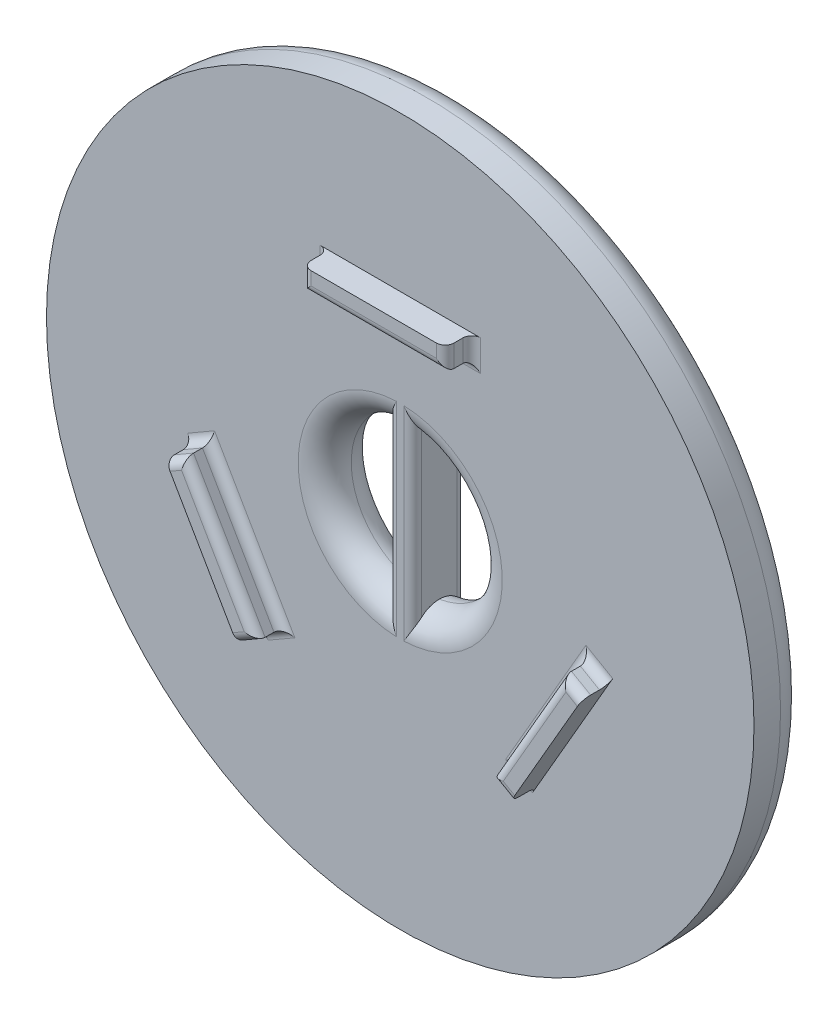
SolidWorks part; units mm, degrees
ref_plane "Front Plane" through (0, 0, 0) normal (0, 0, 1) x (1, 0, 0)
ref_plane "Top Plane" through (0, 0, 0) normal (0, 1, 0) x (1, 0, 0)
ref_plane "Right Plane" through (0, 0, 0) normal (1, 0, 0) x (0, 0, -1)
sketch "Sketch1" plane through (0, 0, 0) normal (0, 0, 1) x (1, 0, 0)
  line L4 (1.4118, -15.9376) -> (1.4118, 15.9376)
  line L8 (-1.4118, 15.9376) -> (-1.4118, -15.9376)
  circle A0 centre (0, 0) radius 40
  arc A1 (-1.4118, 15.9376) -> (-1.4118, -15.9376) centre (0, 0) ccw
  arc A2 (1.4118, -15.9376) -> (1.4118, 15.9376) centre (0, 0) ccw
  dimension "D1" = 80
  dimension "D2" = 24
sketch "Sketch3" plane through (0, 0, 0) normal (0, 0, 1) x (1, 0, 0)
  line L1 (-18.4752, -20) -> (-11.547, -20)
  line L3 (13.2791, -17) -> (17.3205, -10)
  line L4 (-13.2791, -17) -> (-17.3205, -10)
  line L6 (17.3205, -10) -> (21.362, -3)
  line L7 (21.362, -3) -> (13.2791, -17)
  line L8 (0, 20) -> (8.0829, 20)
  line L9 (8.0829, 20) -> (-8.0829, 20)
  line L10 (-17.3205, -10) -> (-21.362, -3)
  line L11 (-21.362, -3) -> (-13.2791, -17)
  line L12 (21.362, -3) -> (26.5581, -6)
  line L13 (0, 20) -> (-8.0829, 20)
  line L15 (0, 26) -> (-8.0829, 26)
  line L16 (-8.0829, 20) -> (-8.0829, 26)
  line L17 (0, 20) -> (8.0829, 20)
  line L19 (0, 26) -> (8.0829, 26)
  line L20 (8.0829, 20) -> (8.0829, 26)
  line L21 (26.5581, -6) -> (18.4752, -20)
  line L22 (18.4752, -20) -> (13.2791, -17)
  line L23 (-21.362, -3) -> (-26.5581, -6)
  line L24 (-26.5581, -6) -> (-18.4752, -20)
  line L25 (-18.4752, -20) -> (-13.2791, -17)
  line L26 (0, 20) -> (0, 0)
  circle A0 centre (0, 0) radius 40 construction
  dimension "D2" = 20
  dimension "D4" = 6
  dimension "D5" = 6
  dimension "D6" = 6
extrude "Boss-Extrude2" add sketch "Sketch3" along normal blind 3 contours L8 L20 L19 L15 L16 L9 | L22 L21 L12 L6 L3 | L24 L25 L4 L10 L23 region at (19.9186, -11.5, 0) region at (-19.9186, -11.5, 0) region at (0, 23, 0)
extrude "Boss-Extrude3" add sketch "Sketch1" against normal blind 6
fillet "Fillet1" radius 3 1 edges at (40, 0, -6)
fillet "Fillet2" radius 3 2 edges at (16, 0, -6) (-16, 0, -6)
fillet "Fillet3" radius 1 2 edges at (-1.4118, 0, -6) (1.4118, 0, -6)
fillet "Fillet4" radius 1 2 edges at (1.4118, 0, 0) (-1.4118, 0, 0)
fillet "Fillet5" radius 3 2 edges at (16, 0, 0) (-16, 0, 0)
fillet "Fillet6" radius 1 9 edges at (8.0829, 23, 3) (0, 20, 3) (-8.0829, 23, 3) (-17.3205, -10, 3) (-15.8771, -18.5, 3) (-23.96, -4.5, 3) (17.3205, -10, 3) (15.8771, -18.5, 3) (23.96, -4.5, 3)
fillet "Fillet7" radius 1 3 edges at (8.0829, 23, 0) (0, 20, 0) (-8.0829, 23, 0)
fillet "Fillet8" radius 1 3 edges at (23.96, -4.5, 0) (17.3205, -10, 0) (15.8771, -18.5, 0)
fillet "Fillet9" radius 1 3 edges at (-15.8771, -18.5, 0) (-17.3205, -10, 0) (-23.96, -4.5, 0)
sketch "Sketch4" plane through (0, 0, 3) normal (0, 0, 1) x (1, 0, 0)
  line L0 (7.0829, 26) -> (-7.0829, 26)
  line L1 (-9.0829, 26) -> (9.0829, 26) construction
  line L2 (-7.0829, 26) -> (7.0829, 26) construction
  line L3 (17.9752, -20.866) -> (27.0581, -5.134)
  line L4 (27.0581, -5.134) -> (24.027, -3.384)
  line L5 (20.9959, -1.634) -> (27.0581, -5.134) construction
  line L6 (24.027, -3.384) -> (14.9441, -19.116)
  line L7 (17.9752, -20.866) -> (11.913, -17.366) construction
  line L8 (14.9441, -19.116) -> (17.9752, -20.866)
  line L9 (9.0829, 26) -> (-9.0829, 26)
  line L10 (-9.0829, 26) -> (-9.0829, 22.5)
  line L11 (-9.0829, 19) -> (-9.0829, 26) construction
  line L12 (-9.0829, 22.5) -> (9.0829, 22.5)
  line L13 (9.0829, 26) -> (9.0829, 19) construction
  line L14 (9.0829, 22.5) -> (9.0829, 26)
  line L15 (-17.9752, -20.866) -> (-14.9441, -19.116)
  line L16 (-11.913, -17.366) -> (-17.9752, -20.866) construction
  line L17 (-14.9441, -19.116) -> (-24.027, -3.384)
  line L18 (-27.0581, -5.134) -> (-20.9959, -1.634) construction
  line L19 (-24.027, -3.384) -> (-27.0581, -5.134)
  line L20 (-27.0581, -5.134) -> (-17.9752, -20.866)
  line M2 (7.0829, 21) -> (7.0829, 26)
  line M3 (7.0829, 26) -> (-7.0829, 26)
  line M4 (-7.0829, 26) -> (-7.0829, 21)
  dimension "D1" = 14.1658
extrude "Cut-Extrude1" cut sketch "Sketch4" against normal blind 3 contours L6 L8 L3 L4 | L12 M4 M2 M3 | L19 L20 L15 L17 | L12 L14 L9 M2 | L10 L12 L9 M4 region at (0, 24.25, 3) region at (8.0829, 24.25, 3) region at (-8.0829, 24.25, 3) region at (21.0011, -12.125, 3) region at (-21.0011, -12.125, 3)
sketch "Sketch5" plane through (0, 0, 0) normal (0, 0, 1) x (1, 0, 0)
  circle A0 centre (0, 0) radius 8.5392
  circle A1 centre (0, 0) radius 19
extrude "Boss-Extrude4" add sketch "Sketch5" against normal blind 6
fillet "Fillet10" radius 3 4 edges at (8.5392, 0, -6) (-8.5392, 0, -6) (-8.5392, 0, 0) (8.5392, 0, 0)
